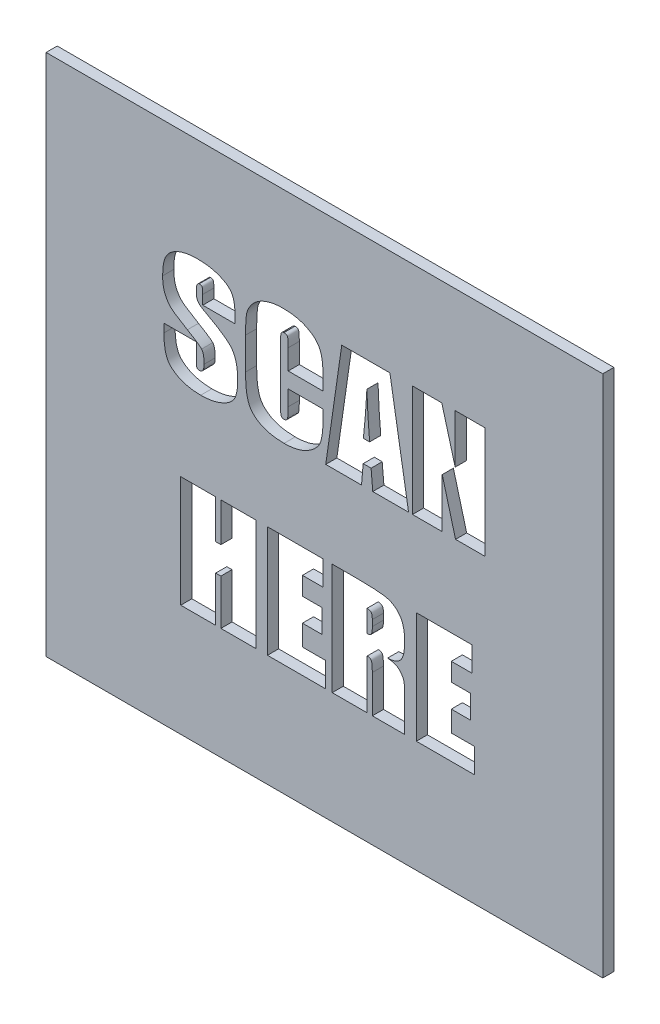
SolidWorks part; units mm, degrees
ref_plane "Front Plane" through (0, 0, 0) normal (0, 0, 1) x (1, 0, 0)
ref_plane "Top Plane" through (0, 0, 0) normal (0, 1, 0) x (1, 0, 0)
ref_plane "Right Plane" through (0, 0, 0) normal (1, 0, 0) x (0, 0, -1)
sketch "Sketch1" plane through (0, 0, 0) normal (0, 1, 0) x (1, 0, 0)
  line L1 (-50, -75) -> (50, -75)
  line L2 (-50, -75) -> (-50, 75)
  line L3 (-50, 75) -> (50, 75)
  line L4 (50, -75) -> (50, 75)
  line L5 (-50, -75) -> (50, 75) construction
  line L6 (-50, 75) -> (50, -75) construction
  point P0 (0, 0)
  dimension "D1" = 100
  dimension "D2" = 150
extrude "Boss-Extrude1" add sketch "Sketch1" along normal blind 150
sketch "Sketch13" plane through (50, 0, 0) normal (1, 0, 0) x (0, 0, -1)
  line L0 (-45, 40) -> (20, 0)
  line L1 (-75, 0) -> (-45, 0)
  line L2 (-75, 0) -> (-75, 40)
  line L3 (-75, 40) -> (-45, 40)
  line L5 (-75, 0) -> (75, 0) construction
  line L8 (-45, 0) -> (20, 0)
  dimension "D1" = 30
  dimension "D2" = 40
  dimension "D3" = 55
extrude "Cut-Extrude7" cut sketch "Sketch13" against normal up to next
shell "Shell1" thickness 5 removed face at (0, 150, 0)
sketch "Sketch3" plane through (0, 0, 0) normal (0, -1, 0) x (1, 0, 0)
  line L1 (50, 45) -> (50, 75) construction
  circle A0 centre (0, 60) radius 4
  circle A1 centre (-5, 50) radius 1.5
  circle A2 centre (5, 50) radius 1.5
  dimension "D3" = 8
  dimension "D4" = 3
  dimension "D5" = 10
  dimension "D7" = 10
  dimension "D8" = 5
  dimension "D1" = 60
  dimension "D2" = 50
extrude "Cut-Extrude2" cut sketch "Sketch3" against normal up to next
sketch "Sketch5" plane through (0, 0, 75) normal (0, 0, 1) x (1, 0, 0)
  line L0 (50, 150) -> (50, 40) construction
  line L1 (-25, 50) -> (25, 50)
  line L2 (-25, 50) -> (-25, 97)
  line L3 (-25, 97) -> (25, 97)
  line L4 (25, 50) -> (25, 97)
  line L5 (-25, 50) -> (25, 97) construction
  line L6 (-25, 97) -> (25, 50) construction
  line L7 (-50, 150) -> (50, 150) construction
  point P0 (0, 73.5)
  dimension "D1" = 50
  dimension "D2" = 47
  dimension "D3" = 50
  dimension "D4" = 76.5
extrude "Boss-Extrude3" add sketch "Sketch5" along normal blind 1
sketch "Sketch8" plane through (0, 0, 75) normal (0, 0, 1) x (1, 0, 0)
  line L0 (-50, 150) -> (-50, 40) construction
  line L1 (-25, 100) -> (25, 100)
  line L2 (-25, 100) -> (-25, 139)
  line L3 (-25, 139) -> (25, 139)
  line L4 (25, 100) -> (25, 139)
  line L5 (-25, 100) -> (25, 139) construction
  line L6 (-25, 139) -> (25, 100) construction
  line L7 (-50, 150) -> (50, 150) construction
  point P0 (0, 119.5)
  dimension "D1" = 50
  dimension "D2" = 39
  dimension "D3" = 50
  dimension "D4" = 50
extrude "Cut-Extrude3" cut sketch "Sketch8" against normal up to next
sketch "Sketch18" plane through (0, 0, 70) normal (0, 0, -1) x (-1, 0, 0)
  line L0 (-25, 139) -> (25, 139) construction
  line L1 (30, 99) -> (-26, 99)
  line L2 (30, 99) -> (30, 140)
  line L3 (30, 140) -> (-26, 140)
  line L4 (-26, 99) -> (-26, 140)
  line L6 (-25, 100) -> (-25, 139) construction
  line L7 (25, 139) -> (25, 100) construction
  dimension "D1" = 1
  dimension "D2" = 41
  dimension "D3" = 1
  dimension "D4" = 5
extrude "Cut-Extrude9" cut sketch "Sketch18" against normal blind 2
sketch "Sketch20" plane through (0, 0, 76) normal (0, 0, 1) x (1, 0, 0)
  line L0 (25, 97) -> (-25, 97) construction
  line L1 (-23, 96) -> (23, 96)
  line L2 (-23, 96) -> (-23, 51)
  line L3 (-23, 51) -> (23, 51)
  line L4 (23, 96) -> (23, 51)
  line L5 (-25, 50) -> (25, 50) construction
  line L6 (25, 50) -> (25, 97) construction
  line L7 (-25, 97) -> (-25, 50) construction
  dimension "D1" = 1
  dimension "D2" = 1
  dimension "D3" = 2
  dimension "D4" = 2
extrude "Cut-Extrude10" cut sketch "Sketch20" against normal blind 15 from offset 4 offset against normal yes
sketch "Sketch21" plane through (0, 45, 0) normal (0, 1, 0) x (1, 0, 0)
  line L1 (9, -52.5) -> (-9, -52.5)
  line L2 (9, -52.5) -> (9, -37.5)
  line L3 (9, -37.5) -> (-9, -37.5)
  line L4 (-9, -52.5) -> (-9, -37.5)
  circle A0 centre (5, -50) radius 1.5 construction
  circle A1 centre (-5, -50) radius 1.5 construction
  dimension "D3" = 4
  dimension "D1" = 4
  dimension "D2" = 2.5
  dimension "D4" = 15
extrude "Cut-Extrude11" cut sketch "Sketch21" against normal blind 2.5
sketch "Sketch22" plane through (-45, 0, 0) normal (1, 0, 0) x (0, 0, -1)
  line L0 (70, 150) -> (-70, 150) construction
  line L5 (70, 150) -> (70, 5) construction
  line L7 (-43.5848, 45) -> (21.4152, 5) construction
  line L8 (10, 150) -> (10, 12.0247)
  line L11 (10, 150) -> (5, 150)
  line L14 (5, 150) -> (5, 15.1017)
  line L15 (5, 15.1017) -> (10, 12.0247)
  dimension "D1" = 60
  dimension "D3" = 5
extrude "Boss-Extrude6" add sketch "Sketch22" along normal blind 5
mirror "Mirror2" about plane through (0, 0, 0) normal (1, 0, 0) of "Boss-Extrude6"
sketch "Sketch23" plane through (-45, 0, 0) normal (1, 0, 0) x (0, 0, -1)
  line L0 (16, 150) -> (21, 150)
  line L1 (70, 150) -> (10, 150) construction
  line L3 (21, 150) -> (21, 5.2555)
  line L4 (21, 5.2555) -> (16, 8.3324)
  line L6 (10, 12.0247) -> (10, 150) construction
  line L7 (16, 150) -> (16, 8.3324)
  line L8 (10, 12.0247) -> (21.4152, 5) construction
  dimension "D1" = 6
  dimension "D2" = 5
extrude "Boss-Extrude7" add sketch "Sketch23" along normal up to next
sketch "Sketch24" plane through (-45, 0, 0) normal (1, 0, 0) x (0, 0, -1)
  line L0 (70, 150) -> (70, 5) construction
  line L1 (70, 135) -> (67, 135)
  line L2 (70, 135) -> (70, 105)
  line L3 (70, 105) -> (67, 105)
  line L4 (67, 135) -> (67, 105)
  line L5 (70, 150) -> (21, 150) construction
  line L6 (70, 5) -> (21.4152, 5) construction
  line L7 (70, 20) -> (67, 20)
  line L8 (70, 20) -> (70, 50)
  line L9 (70, 50) -> (67, 50)
  line L10 (67, 20) -> (67, 50)
  dimension "D1" = 15
  dimension "D2" = 30
  dimension "D3" = 3
  dimension "D4" = 15
extrude "Cut-Extrude12" cut sketch "Sketch24" against normal through all both and the other way through all
sketch "Sketch28" plane through (0, 0, 76) normal (0, 0, 1) x (1, 0, 0)
  line L0 (-25, 73.5) -> (25, 73.5) construction
  line L1 (-25, 97) -> (-25, 50) construction
  line L2 (25, 50) -> (25, 97) construction
  line L3 (-25, 77.511) -> (25, 77.511) construction
  text T0 "SCAN\r\nHERE" font "Impact" height 10
extrude "Cut-Extrude14" cut sketch "Sketch28" against normal blind 1
sketch "Sketch30" plane through (0, 0, -75) normal (0, 0, -1) x (-1, 0, 0)
  text T0 "IBE VAN DE VEIRE\r\nSTEF GIELEN" font "Comic Sans MS" height 5
extrude "Cut-Extrude16" cut sketch "Sketch30" against normal blind 1
sketch "Sketch32" plane through (0, 150, 0) normal (0, 1, 0) x (1, 0, 0)
  line L0 (-50, 75) -> (-50, -75) construction
  line L1 (50, 75) -> (-50, 75) construction
  line L2 (-50, -75) -> (50, -75) construction
  line L3 (50, -75) -> (50, 75) construction
  circle A0 centre (-47, 72) radius 1.225
  circle A1 centre (-47, -72) radius 1.225
  circle A2 centre (47, -72) radius 1.225
  circle A3 centre (47, 72) radius 1.225
  dimension "D1" = 2.45
  dimension "D2" = 3
  dimension "D3" = 3
  dimension "D4" = 2.45
  dimension "D5" = 3
  dimension "D6" = 3
  dimension "D7" = 2.45
  dimension "D8" = 3
  dimension "D9" = 3
  dimension "D10" = 2.45
  dimension "D11" = 3
  dimension "D12" = 3
extrude "Cut-Extrude17" cut sketch "Sketch32" against normal blind 20
sketch "Sketch33" plane through (0, 150, 0) normal (0, 1, 0) x (1, 0, 0)
  line L1 (-45, 5) -> (45, 5)
  line L2 (-45, 5) -> (-45, 21)
  line L3 (-45, 21) -> (45, 21)
  line L4 (45, 5) -> (45, 21)
extrude "Cut-Extrude18" cut sketch "Sketch33" against normal blind 40
sketch "Sketch34" plane through (0, 150, 0) normal (0, 1, 0) x (1, 0, 0)
  line L0 (50, 75) -> (-50, 75) construction
  line L1 (-45, 75) -> (50, 75)
  line L2 (-45, 75) -> (-45, -75)
  line L3 (-45, -75) -> (50, -75)
  line L4 (50, 75) -> (50, -75)
sketch "Sketch36" plane through (0, 150, 0) normal (0, 1, 0) x (1, 0, 0)
  line L1 (50, 75) -> (-50, 75)
  line L2 (50, 75) -> (50, -75)
  line L3 (50, -75) -> (-50, -75)
  line L4 (-50, 75) -> (-50, -75)
extrude "Cut-Extrude19" cut sketch "Sketch36" against normal through all both and the other way through all
